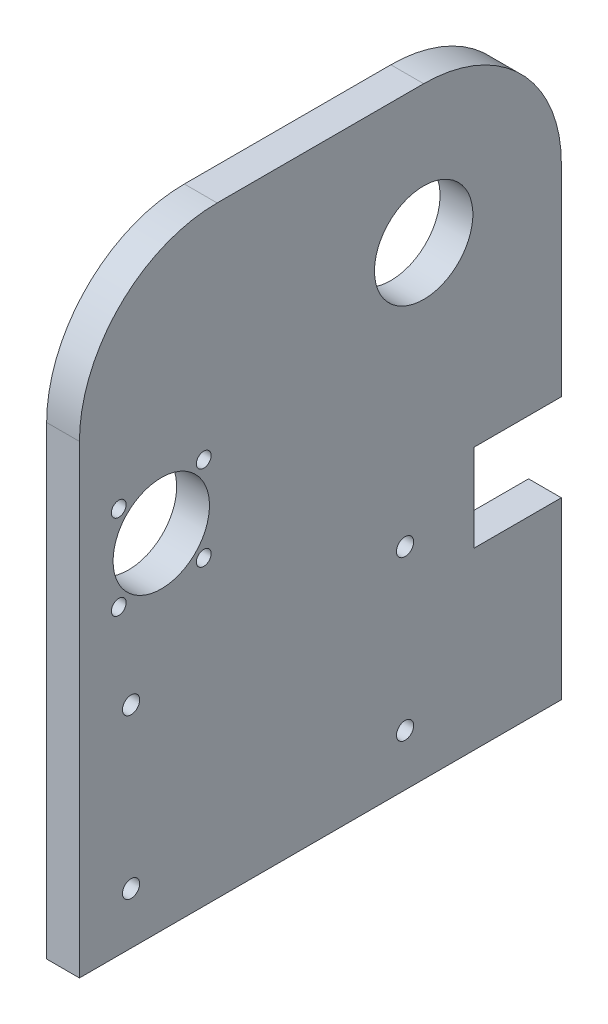
SolidWorks part; units mm, degrees
ref_plane "Front Plane" through (0, 0, 0) normal (0, 0, 1) x (1, 0, 0)
ref_plane "Top Plane" through (0, 0, 0) normal (0, 1, 0) x (1, 0, 0)
ref_plane "Right Plane" through (0, 0, 0) normal (1, 0, 0) x (0, 0, -1)
sketch "Sketch1" plane through (0, 0, 0) normal (0, 1, 0) x (1, 0, 0)
  line L1 (-4.7625, 70) -> (4.7625, 70)
  line L2 (-4.7625, 70) -> (-4.7625, -70)
  line L3 (-4.7625, -70) -> (4.7625, -70)
  line L4 (4.7625, 70) -> (4.7625, -70)
  line L5 (-4.7625, 70) -> (4.7625, -70) construction
  line L6 (-4.7625, -70) -> (4.7625, 70) construction
  point P0 (0, 0)
  dimension "D1" = 140
  dimension "D2" = 9.525
extrude "Boss-Extrude1" add sketch "Sketch1" along normal mid plane 175
sketch "Sketch5" plane through (-4.7625, 0, 0) normal (-1, 0, 0) x (0, 0, 1)
  line L1 (-70, 87.5) -> (-70, -87.5) construction
  line L2 (-70, -11.2746) -> (-44.6, -11.2746)
  line L3 (-70, -11.2746) -> (-70, -36.6746)
  line L4 (-70, -36.6746) -> (-44.6, -36.6746)
  line L5 (-70, -87.5) -> (70, -87.5) construction
  line L6 (-44.6, -11.2746) -> (-44.6, -36.6746)
  dimension "D3" = 25.4
  dimension "D1" = 50.8254
  dimension "D2" = 25.4
sketch "Sketch3" plane through (-4.7625, 0, 0) normal (-1, 0, 0) x (0, 0, 1)
  line L0 (46.229, 12.5) -> (57.4989, 23.77) construction
  line L2 (-70, 87.5) -> (-70, -87.5) construction
  line L3 (-45.4613, 12.5) -> (44.137, 12.5) construction
  line L6 (46.229, 26.0113) -> (46.229, -23.3547) construction
  line L7 (-70, 87.5) -> (70, 87.5) construction
  circle A0 centre (-30, 47.5) radius 14.29
  circle A1 centre (33.8811, 24.8479) radius 2.15
  circle A2 centre (58.5768, 24.8479) radius 2.15
  circle A3 centre (33.8811, 0.1521) radius 2.15
  circle A4 centre (58.5768, 0.1521) radius 2.15
  circle A5 centre (46.229, 12.5) radius 14
  circle A6 centre (46.229, 12.5) radius 17.4625 construction
  dimension "D1" = 28.58
  dimension "D2" = 40
  dimension "D3" = 45
  dimension "D4" = 12.3479
  dimension "D7" = 28
  dimension "D8" = 4.3
  dimension "D10" = 35
  dimension "Bolt circle" = 34.925
  dimension "D5" = 83.88
  dimension "D9" = 40
extrude "Cut-Extrude2" cut sketch "Sketch3" against normal blind 28.575
extrude "Cut-Extrude4" cut sketch "Sketch5" against normal through all
ref_axis "Axis1" through (4.7625, 47.5, -30) along (-1, 0, 0)
hole_wizard "M6 Tapped Hole1" positions "Sketch7" profile "Sketch6" tap size "M6" standard "DIN"
sketch "Sketch7" plane through (0, 0, -44.6) normal (0, 0, -1) x (-1, 0, 0)
  line L1 (-4.7625, -36.6746) -> (4.7625, -36.6746) construction
  point P0 (0, -23.9746)
  dimension "D1" = 12.7
sketch "Sketch6" plane through (0, -23.9746, -44.6) normal (1, 0, 0) x (0, 1, 0)
  line L0 (0, 0) -> (0, 11.5022)
  line L1 (0, 11.5022) -> (2.5, 10)
  line L2 (2.5, 10) -> (2.5, 0)
  line L5 (2.5, 0) -> (0, 0)
  line L10 (0, 11.5022) -> (-2.5, 10) construction
  line L11 (0, -6.35) -> (0, 107.95) construction
  dimension "Tap Drill Dia." = 5
  dimension "Tap Drill Depth" = 10
  dimension "Drill Angle" = 118
cosmetic thread "Hole Thread1" parameters "D1"=10, "D2"=6
hole_wizard "M6 Tapped Hole2" positions "Sketch9" profile "Sketch8" tap size "M6" standard "DIN" end condition through all
sketch "Sketch9" plane through (-4.7625, 0, 0) normal (-1, 0, 0) x (0, 0, 1)
  line L0 (-44.6, -36.6746) -> (-44.6, -11.2746) construction
  line L1 (-70, -36.6746) -> (-70, -87.5) construction
  line L2 (70, 87.5) -> (70, -87.5) construction
  line L3 (-44.6, -11.2746) -> (-70, -11.2746) construction
  line L5 (-70, -87.5) -> (70, -87.5) construction
  point P0 (-24.6, -26.2746)
  point P2 (55, -26.2746)
  point P4 (-24.6, -72.5)
  point P6 (55, -72.5)
  dimension "D1" = 20
  dimension "D2" = 45.4
  dimension "D3" = 15
  dimension "D4" = 15
  dimension "D5" = 15
  dimension "D6" = 15
  dimension "D7" = 15
  dimension "D8" = 15
sketch "Sketch8" plane through (-4.7625, -26.2746, -24.6) normal (0, 1, 0) x (0, 0, 1)
  line L0 (0, 0) -> (0, 9.525)
  line L1 (0, 9.525) -> (2.5, 9.525)
  line L2 (2.5, 9.525) -> (2.5, 0)
  line L5 (2.5, 0) -> (0, 0)
  line L11 (0, -6.35) -> (0, 107.95) construction
  dimension "Thru Tap Drill Dia." = 5
  dimension "Thru Tap Drill Depth" = 9.525
cosmetic thread "Hole Thread2" parameters "D2"=6
cosmetic thread "Hole Thread3" parameters "D2"=6
cosmetic thread "Hole Thread4" parameters "D2"=6
cosmetic thread "Hole Thread5" parameters "D2"=6
fillet "Fillet1" radius 40 2 edges at (0, 87.5, 70) (0, 87.5, -70)
